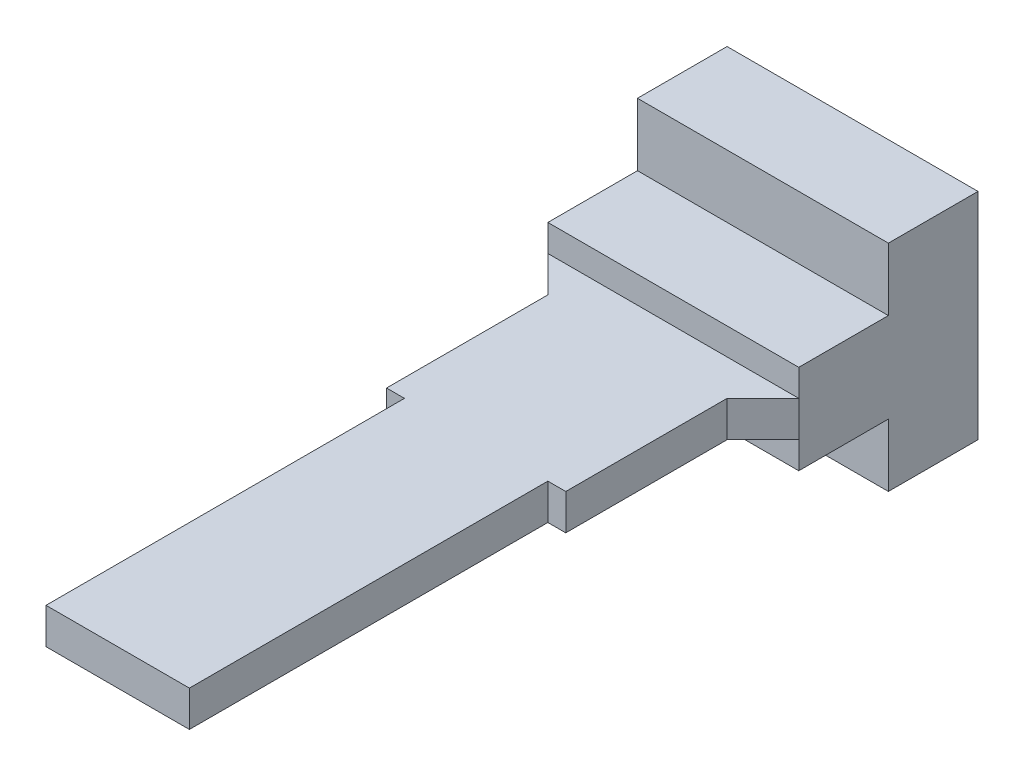
SolidWorks part; units mm, degrees
ref_plane "정면" through (0, 0, 0) normal (0, 0, 1) x (1, 0, 0)
ref_plane "윗면" through (0, 0, 0) normal (0, 1, 0) x (1, 0, 0)
ref_plane "우측면" through (0, 0, 0) normal (1, 0, 0) x (0, 0, -1)
sketch "스케치1" plane through (0, 0, 0) normal (0, 0, 1) x (1, 0, 0)
  line L1 (-3.5, -3) -> (3.5, -3)
  line L2 (-3.5, -3) -> (-3.5, 3)
  line L3 (-3.5, 3) -> (3.5, 3)
  line L4 (3.5, -3) -> (3.5, 3)
  line L5 (-3.5, -3) -> (3.5, 3) construction
  line L6 (-3.5, 3) -> (3.5, -3) construction
  point P0 (0, 0)
  dimension "D1" = 7
  dimension "D2" = 6
extrude "보스-돌출1" add sketch "스케치1" along normal blind 2.5
sketch "스케치2" plane through (0, 0, 2.5) normal (0, 0, 1) x (1, 0, 0)
  line L0 (3.5, -3) -> (3.5, 3) construction
  line L1 (-3.5, -1.25) -> (3.5, -1.25)
  line L2 (-3.5, -1.25) -> (-3.5, 1.25)
  line L3 (-3.5, 1.25) -> (3.5, 1.25)
  line L4 (3.5, -1.25) -> (3.5, 1.25)
  line L5 (-3.5, -1.25) -> (3.5, 1.25) construction
  line L6 (-3.5, 1.25) -> (3.5, -1.25) construction
  point P0 (0, 0)
  dimension "2.5" = 2.5
extrude "보스-돌출2" add sketch "스케치2" along normal blind 2.5
sketch "스케치3" plane through (0, 0, 5) normal (0, 0, 1) x (1, 0, 0)
  line L0 (-3.5, 1.25) -> (-3.5, -1.25) construction
  line L1 (3.5, -0.5) -> (-3.5, -0.5)
  line L2 (3.5, -0.5) -> (3.5, 0.5)
  line L3 (3.5, 0.5) -> (-3.5, 0.5)
  line L4 (-3.5, -0.5) -> (-3.5, 0.5)
  line L5 (3.5, -0.5) -> (-3.5, 0.5) construction
  line L6 (3.5, 0.5) -> (-3.5, -0.5) construction
  point P0 (0, 0)
  dimension "D1" = 1
extrude "보스-돌출3" add sketch "스케치3" along normal blind 1
sketch "스케치4" plane through (0, 0, 6) normal (0, 0, 1) x (1, 0, 0)
  line L0 (3.5, 0.5) -> (-3.5, 0.5) construction
  line L1 (2.5, -0.5) -> (-2.5, -0.5)
  line L2 (2.5, -0.5) -> (2.5, 0.5)
  line L3 (2.5, 0.5) -> (-2.5, 0.5)
  line L4 (-2.5, -0.5) -> (-2.5, 0.5)
  line L5 (2.5, -0.5) -> (-2.5, 0.5) construction
  line L6 (2.5, 0.5) -> (-2.5, -0.5) construction
  point P1 (0, 0)
  dimension "D1" = 5
extrude "보스-돌출4" add sketch "스케치4" along normal blind 4.5
sketch "스케치5" plane through (0, 0, 10.5) normal (0, 0, 1) x (1, 0, 0)
  line L0 (2.5, 0.5) -> (-2.5, 0.5) construction
  line L1 (2, -0.5) -> (-2, -0.5)
  line L2 (2, -0.5) -> (2, 0.5)
  line L3 (2, 0.5) -> (-2, 0.5)
  line L4 (-2, -0.5) -> (-2, 0.5)
  line L5 (2, -0.5) -> (-2, 0.5) construction
  line L6 (2, 0.5) -> (-2, -0.5) construction
  point P0 (0, 0)
  dimension "D1" = 4
extrude "보스-돌출5" add sketch "스케치5" along normal blind 10
chamfer "모따기1" distance 1 angle 45 2 edges at (3.5, 0, 6) (-3.5, 0, 6)
